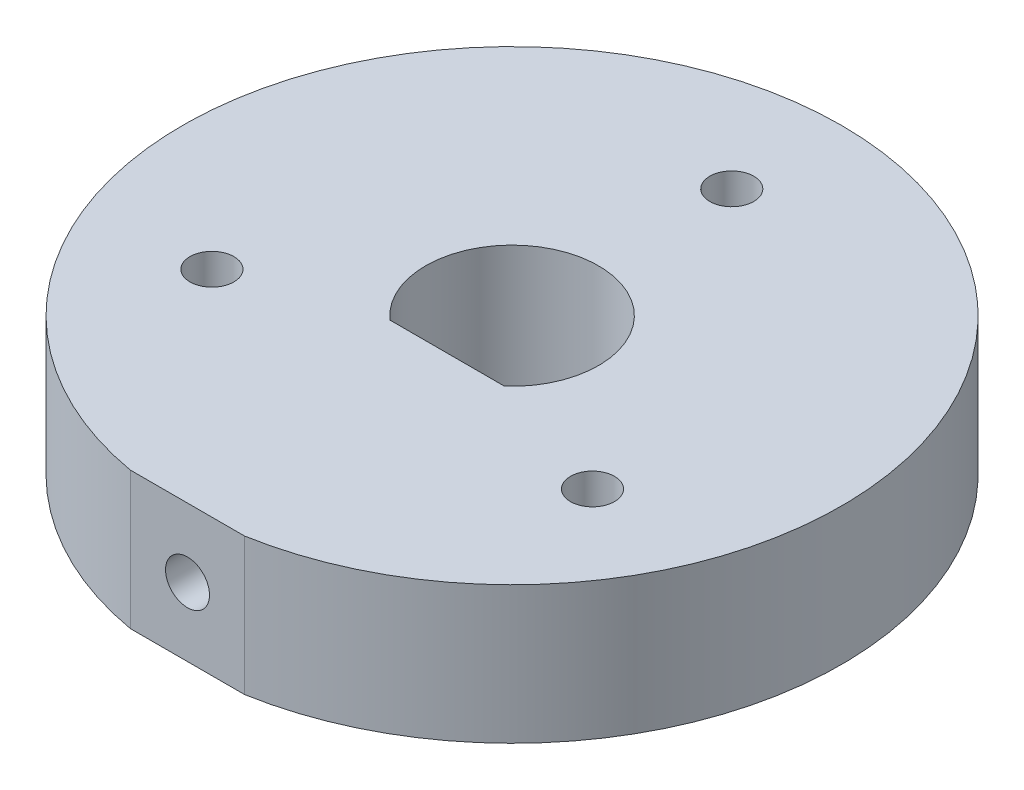
SolidWorks part; units mm, degrees
ref_plane "Front Plane" through (0, 0, 0) normal (0, 0, 1) x (1, 0, 0)
ref_plane "Top Plane" through (0, 0, 0) normal (0, 1, 0) x (1, 0, 0)
ref_plane "Right Plane" through (0, 0, 0) normal (1, 0, 0) x (0, 0, -1)
sketch "Sketch1" plane through (0, 0, 0) normal (0, 1, 0) x (1, 0, 0)
  line L0 (-2.6458, -15.0086) -> (2.6458, -15.0086)
  line L1 (-2.6458, -3) -> (2.6458, -3)
  line L2 (0, -3) -> (0, 10.16) construction
  arc A0 (-2.6458, -15.0086) -> (2.6458, -15.0086) centre (0, 0) cw
  arc A1 (-2.6458, -3) -> (2.6458, -3) centre (0, 0) cw
  circle A2 centre (0, 10.16) radius 1.016
  circle A3 centre (8.7988, -5.08) radius 1.016
  circle A4 centre (-8.7988, -5.08) radius 1.016
  dimension "D1" = 4
  dimension "D3" = 15.24
  dimension "D4" = 2.032
  dimension "D2" = 3
  dimension "D5" = 10.16
  dimension "D6" = 3
extrude "Boss-Extrude1" add sketch "Sketch1" along normal blind 6.35
sketch "Sketch2" plane through (0, 0, 15.0086) normal (0, 0, 1) x (1, 0, 0)
  line L0 (-2.6458, 6.35) -> (-2.6458, 0) construction
  line L1 (-2.6458, 6.35) -> (2.6458, 6.35) construction
  circle A0 centre (0, 3.175) radius 1.016
  point P4 (-2.6458, 3.175)
  point P7 (0, 6.35)
  dimension "D1" = 2.032
extrude "Cut-Extrude1" cut sketch "Sketch2" against normal up to next
